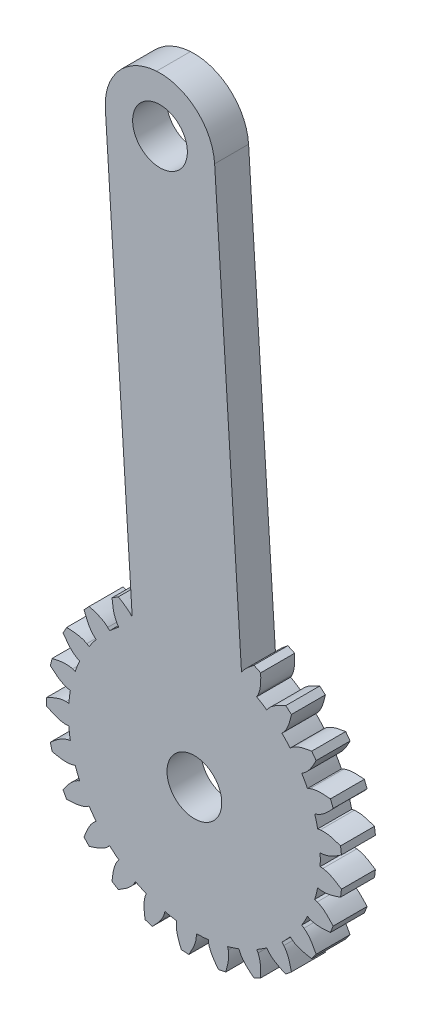
SolidWorks part; units mm, degrees
material "Teak"
ref_plane "Front Plane" through (0, 0, 0) normal (0, 0, 1) x (1, 0, 0)
ref_plane "Top Plane" through (0, 0, 0) normal (0, 1, 0) x (1, 0, 0)
ref_plane "Right Plane" through (0, 0, 0) normal (1, 0, 0) x (0, 0, -1)
sketch "Sketch1" plane through (0, 0, 0) normal (0, 0, 1) x (1, 0, 0)
  line L0 (0, 0) -> (0, 12.5) construction
  line L1 (0, 12.5) -> (-13.702, 12.5) construction
  line L2 (0, 12.5) -> (-10.9203, 8.5253) construction
  line L3 (-4.0174, 11.0378) -> (0, 0) construction
  line L4 (-6.6756, 9.6648) -> (0, 0) construction
  line L5 (-6.6756, 9.6648) -> (-0.6895, 13.7995) construction
  line L6 (0, 0) -> (-2.089, 11.5589) construction
  line L7 (-2.089, 11.5589) -> (0.15, 11.9635) construction
  circle A0 centre (0, 0) radius 12.5 construction
  circle A1 centre (0, 0) radius 11.7462 construction
  arc A2 (-4.0174, 11.0378) -> (-6.6756, 9.6648) centre (0, 0) ccw
  arc A3 (-4.0174, 11.0378) -> (-2.089, 11.5589) centre (0, 0) cw
  arc A4 (-4.0174, 11.0378) -> (0.1751, 11.7449) centre (0, 0) cw
  dimension "D1" = 25
  dimension "D2" = 20
  dimension "D3" = 90
  dimension "D4" = 4.2753
  dimension "D5" = 3
  dimension "D6" = 90
  dimension "D7" = 7.2753
  dimension "D8" = 2
  dimension "D9" = 2.2753
  dimension "D10" = 4.2753
sketch "Sketch2" plane through (0, 0, 0) normal (0, 0, 1) x (1, 0, 0)
  line L0 (0, 12.5) -> (0, 0) construction
  line L1 (0, 0) -> (-0.9641, 15.3243) construction
  line L2 (0.1751, 11.7449) -> (0.1751, 11.4949)
  line L3 (0.1751, 11.4949) -> (0, 0) construction
  line L4 (-1.6457, 11.6303) -> (-1.6144, 11.3823)
  line L5 (-1.1873, 13.4477) -> (-0.5075, 13.4905)
  circle A0 centre (0, 0) radius 13.5 construction
  arc A1 (-1.6144, 11.3823) -> (0.1751, 11.4949) centre (0, 0) cw
  spline S0 degree 3 poles (-0.5075, 13.4905) (-0.3221, 13.1763) (0.0007, 12.6135) (0.1589, 12.0044) (0.1751, 11.7449) knots 0.163671 0.163671 0.163671 0.163671 0.654331 1 1 1 1
  spline S1 degree 3 poles (-1.1873, 13.4477) (-1.3319, 13.1128) (-1.5815, 12.5139) (-1.6622, 11.8899) (-1.6457, 11.6303) knots 0.163671 0.163671 0.163671 0.163671 0.654331 1 1 1 1
  point P19 (-0.8022, 12.7502)
  dimension "D2" = 27
  dimension "D1" = 3.6
  dimension "D3" = 0.25
extrude "Boss-Extrude2" add sketch "Sketch2" along normal blind 3.1
sketch "Sketch4" plane through (0, 0, 0) normal (0, 0, 1) x (1, 0, 0)
  circle A0 centre (0, 0) radius 11.4962
  circle A1 centre (0, 0) radius 2.5
  dimension "D1" = 5
extrude "Boss-Extrude3" add sketch "Sketch4" along normal through all
pattern_circular "CirPattern1" count 25 over 360 about axis through (0, 0, 3.1) along (0, 0, 1) of "Boss-Extrude2"
sketch "Sketch5" plane through (0, 0, 3.1) normal (0, 0, 1) x (1, 0, 0)
  line L0 (0, 0) -> (-0.8474, 13.4691) construction
  line L1 (0, 0) -> (3.1395, 49.9013) construction
  line L2 (-4.6998, 4.9288) -> (-1.5367, 55.2054)
  line L3 (-4.6998, 4.9288) -> (5.2805, 4.3009)
  line L4 (-1.5367, 55.2054) -> (8.4436, 54.5775)
  line L5 (5.2805, 4.3009) -> (8.4436, 54.5775)
  line L6 (-4.6998, 4.9288) -> (8.4436, 54.5775) construction
  line L7 (-1.5367, 55.2054) -> (5.2805, 4.3009) construction
  line L8 (-11.8264, 6.5016) -> (0, 0) construction
  line L9 (-11.6623, 6.8) -> (-11.9904, 6.2032) construction
  line L10 (0, 0) -> (-9.8379, 9.2384) construction
  line L11 (-9.6048, 9.4867) -> (-10.0711, 8.9902) construction
  line L12 (-0.5075, 13.4905) -> (-1.1873, 13.4477) construction
  circle A0 centre (3.1395, 49.9013) radius 2.5
  point P7 (1.8719, 29.7531)
  dimension "D3" = 5
  dimension "D1" = 7.2
  dimension "D2" = 10
  dimension "D4" = 5
  dimension "D5" = 50
  dimension "D6" = 90
extrude "Boss-Extrude4" [suppressed] add sketch "Sketch5" against normal through all
fillet "Fillet1" [suppressed] radius 5
sketch "Sketch6" plane through (0, 0, 0) normal (0, 0, 1) x (1, 0, 0)
  line L0 (0, 0) -> (-0.8474, 13.4691) construction
  line L1 (0, 0) -> (-3.1395, 49.9013) construction
  line L2 (-5.2805, 4.3009) -> (-8.4436, 54.5775)
  line L3 (-5.2805, 4.3009) -> (4.6998, 4.9288)
  line L4 (-8.4436, 54.5775) -> (1.5367, 55.2054)
  line L5 (4.6998, 4.9288) -> (1.5367, 55.2054)
  line L6 (-5.2805, 4.3009) -> (1.5367, 55.2054) construction
  line L7 (-8.4436, 54.5775) -> (4.6998, 4.9288) construction
  line L8 (-0.5075, 13.4905) -> (-1.1873, 13.4477) construction
  circle A0 centre (-3.1395, 49.9013) radius 2.5
  point P7 (-1.8719, 29.7531)
  dimension "D3" = 5
  dimension "D1" = 0
  dimension "D2" = 10
  dimension "D4" = 5
  dimension "D5" = 50
  dimension "D6" = 90
extrude "Boss-Extrude6" add sketch "Sketch6" along normal through all
fillet "Fillet2" radius 5 2 edges at (-8.4436, 54.5775, 1.55) (1.5367, 55.2054, 1.55)
equation "\"p\"= 25mm"
equation "\"m\"= 1"
equation "\"D1@Sketch1\"=\"p\""
equation "\"D7@Sketch1\"=\"D4@Sketch1\"+\"D5@Sketch1\""
equation "\"D9@Sketch1\"=\"D4@Sketch1\"-\"D8@Sketch1\""
equation "\"D10@Sketch1\"=\"D4@Sketch1\""
equation "\"D1@Sketch2\"=360/(\"p\"/\"m\")/4"
equation "\"D2@Sketch2\"=\"p\"+2*\"m\""
equation "\"D1@CirPattern1\"=\"p\"/\"m\""
equation "\"D1@Sketch5\"=360/(\"p\"/\"m\")/2"
equation "\"D4@Sketch5\"=\"D3@Sketch5\""
